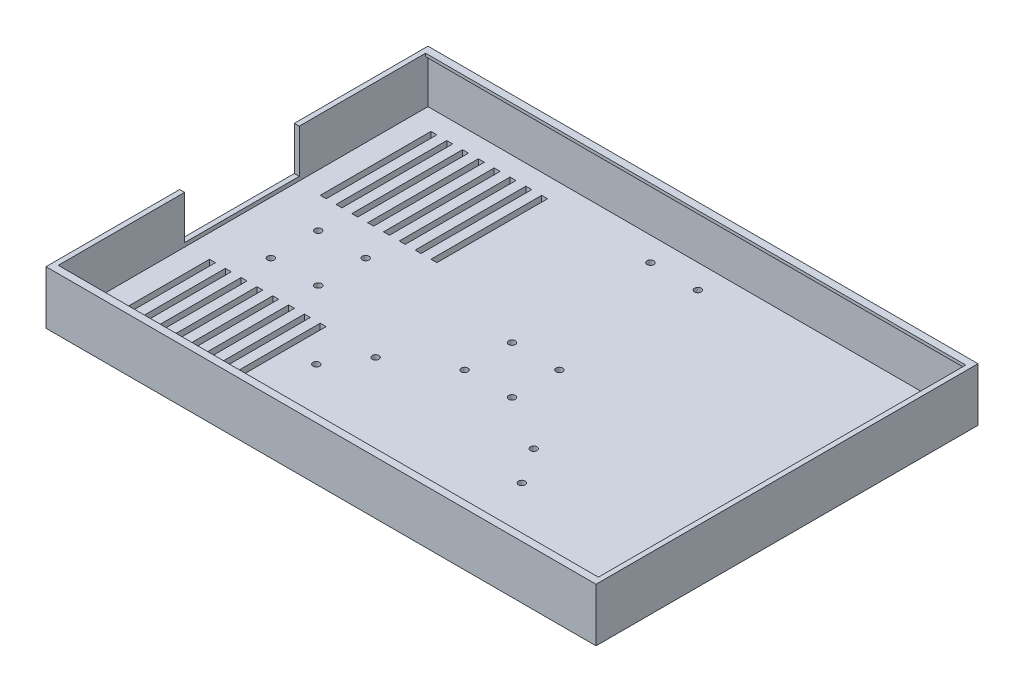
SolidWorks part; units mm, degrees
ref_plane "Front Plane" through (0, 0, 0) normal (0, 0, 1) x (1, 0, 0)
ref_plane "Top Plane" through (0, 0, 0) normal (0, 1, 0) x (1, 0, 0)
ref_plane "Right Plane" through (0, 0, 0) normal (1, 0, 0) x (0, 0, -1)
sketch "Sketch1" plane through (0, 0, 0) normal (0, 1, 0) x (1, 0, 0)
  line L1 (-139.1, -96.6) -> (139.1, -96.6)
  line L2 (-139.1, -96.6) -> (-139.1, 96.6)
  line L3 (-139.1, 96.6) -> (139.1, 96.6)
  line L4 (139.1, -96.6) -> (139.1, 96.6)
  line L5 (-139.1, -96.6) -> (139.1, 96.6) construction
  line L6 (-139.1, 96.6) -> (139.1, -96.6) construction
  point P0 (0, 0)
  dimension "D1" = 278.2
  dimension "D2" = 193.2
extrude "Shell Block" add sketch "Sketch1" along normal blind 27
ref_plane "Shell Front" through (0, 27, 0) normal (0, 1, 0) x (1, 0, 0)
sketch "Sketch2" plane through (0, 27, 0) normal (0, 1, 0) x (1, 0, 0)
  line L1 (-136.6, -92.9) -> (136.6, -92.9)
  line L2 (-136.6, -92.9) -> (-136.6, 92.9)
  line L3 (-136.6, 92.9) -> (136.6, 92.9)
  line L4 (136.6, -92.9) -> (136.6, 92.9)
  line L5 (-136.6, -92.9) -> (136.6, 92.9) construction
  line L6 (-136.6, 92.9) -> (136.6, -92.9) construction
  point P0 (0, 0)
  dimension "D1" = 273.2
  dimension "D2" = 185.8
extrude "Front Opening" cut sketch "Sketch2" against normal blind 1.5
ref_plane "Under Lip" through (0, 25.5, 0) normal (0, 1, 0) x (1, 0, 0)
sketch "Sketch3" plane through (0, 25.5, 0) normal (0, 1, 0) x (1, 0, 0)
  line L1 (-136.6, -94.1) -> (136.6, -94.1)
  line L2 (-136.6, -94.1) -> (-136.6, 94.1)
  line L3 (-136.6, 94.1) -> (136.6, 94.1)
  line L4 (136.6, -94.1) -> (136.6, 94.1)
  line L5 (-136.6, -94.1) -> (136.6, 94.1) construction
  line L6 (-136.6, 94.1) -> (136.6, -94.1) construction
  point P0 (0, 0)
  dimension "D1" = 273.2
  dimension "D2" = 188.2
extrude "Display Pocket" cut sketch "Sketch3" against normal blind 22.5
ref_plane "Back Inner" through (0, 3, 0) normal (0, 1, 0) x (1, 0, 0)
sketch "Sketch4" plane through (0, 3, 0) normal (0, 1, 0) x (1, 0, 0)
  line L1 (-69, 28) -> (-66, 28)
  line L2 (-69, 28) -> (-69, 84)
  line L3 (-69, 84) -> (-66, 84)
  line L4 (-66, 28) -> (-66, 84)
  line L6 (-69, -84) -> (-66, -84)
  line L7 (-69, -84) -> (-69, -28)
  line L8 (-69, -28) -> (-66, -28)
  line L9 (-66, -84) -> (-66, -28)
  line L11 (-77, 28) -> (-74, 28)
  line L12 (-77, 28) -> (-77, 84)
  line L13 (-77, 84) -> (-74, 84)
  line L14 (-74, 28) -> (-74, 84)
  line L16 (-77, -84) -> (-74, -84)
  line L17 (-77, -84) -> (-77, -28)
  line L18 (-77, -28) -> (-74, -28)
  line L19 (-74, -84) -> (-74, -28)
  line L21 (-85, 28) -> (-82, 28)
  line L22 (-85, 28) -> (-85, 84)
  line L23 (-85, 84) -> (-82, 84)
  line L24 (-82, 28) -> (-82, 84)
  line L26 (-85, -84) -> (-82, -84)
  line L27 (-85, -84) -> (-85, -28)
  line L28 (-85, -28) -> (-82, -28)
  line L29 (-82, -84) -> (-82, -28)
  line L31 (-93, 28) -> (-90, 28)
  line L32 (-93, 28) -> (-93, 84)
  line L33 (-93, 84) -> (-90, 84)
  line L34 (-90, 28) -> (-90, 84)
  line L36 (-93, -84) -> (-90, -84)
  line L37 (-93, -84) -> (-93, -28)
  line L38 (-93, -28) -> (-90, -28)
  line L39 (-90, -84) -> (-90, -28)
  line L41 (-101, 28) -> (-98, 28)
  line L42 (-101, 28) -> (-101, 84)
  line L43 (-101, 84) -> (-98, 84)
  line L44 (-98, 28) -> (-98, 84)
  line L46 (-101, -84) -> (-98, -84)
  line L47 (-101, -84) -> (-101, -28)
  line L48 (-101, -28) -> (-98, -28)
  line L49 (-98, -84) -> (-98, -28)
  line L51 (-109, 28) -> (-106, 28)
  line L52 (-109, 28) -> (-109, 84)
  line L53 (-109, 84) -> (-106, 84)
  line L54 (-106, 28) -> (-106, 84)
  line L56 (-109, -84) -> (-106, -84)
  line L57 (-109, -84) -> (-109, -28)
  line L58 (-109, -28) -> (-106, -28)
  line L59 (-106, -84) -> (-106, -28)
  line L61 (-117, 28) -> (-114, 28)
  line L62 (-117, 28) -> (-117, 84)
  line L63 (-117, 84) -> (-114, 84)
  line L64 (-114, 28) -> (-114, 84)
  line L66 (-117, -84) -> (-114, -84)
  line L67 (-117, -84) -> (-117, -28)
  line L68 (-117, -28) -> (-114, -28)
  line L69 (-114, -84) -> (-114, -28)
  line L71 (-125, 28) -> (-122, 28)
  line L72 (-125, 28) -> (-125, 84)
  line L73 (-125, 84) -> (-122, 84)
  line L74 (-122, 28) -> (-122, 84)
  line L76 (-125, -84) -> (-122, -84)
  line L77 (-125, -84) -> (-125, -28)
  line L78 (-125, -28) -> (-122, -28)
  line L79 (-122, -84) -> (-122, -28)
extrude "Vent Slots" cut sketch "Sketch4" against normal blind 4
sketch "Sketch5" plane through (0, 0, 0) normal (1, 0, 0) x (0, 0, -1)
  line L1 (-29, 5) -> (29, 5)
  line L2 (-29, 5) -> (-29, 28)
  line L3 (-29, 28) -> (29, 28)
  line L4 (29, 5) -> (29, 28)
extrude "Cable Exit (-X short side)" cut sketch "Sketch5" against normal blind 140.1
sketch "Sketch6" plane through (0, 3, 0) normal (0, 1, 0) x (1, 0, 0)
  circle A0 centre (-40, -29) radius 1.7
  circle A1 centre (-40, -89) radius 1.7
  circle A2 centre (40, -29) radius 1.7
  circle A3 centre (40, -89) radius 1.7
  circle A4 centre (-52, -47) radius 1.7
  circle A5 centre (-52, -71) radius 1.7
  circle A6 centre (52, -47) radius 1.7
  circle A7 centre (52, -71) radius 1.7
  circle A8 centre (-12, 82) radius 1.7
  circle A9 centre (12, 82) radius 1.7
  circle A10 centre (124, 12) radius 1.7
  circle A11 centre (124, -12) radius 1.7
  circle A12 centre (-12, 12) radius 1.7
  circle A13 centre (-12, -12) radius 1.7
  circle A14 centre (12, 12) radius 1.7
  circle A15 centre (12, -12) radius 1.7
  circle A16 centre (-110, -12) radius 1.7
  circle A17 centre (-110, 12) radius 1.7
  circle A18 centre (-86, -12) radius 1.7
  circle A19 centre (-86, 12) radius 1.7
extrude "Bolt Holes" cut sketch "Sketch6" against normal blind 4
equation "\"DispL\" = 272.0"
equation "\"DispW\" = 187.0"
equation "\"DispT\" = 20.0"
equation "\"Clr\" = 0.6"
equation "\"Wall\" = 2.5"
equation "\"BackT\" = 3.0"
equation "\"CableRoom\" = 4.0"
equation "\"LipW\" = 1.2"
equation "\"LipT\" = 1.5"
equation "\"CableW\" = 58.0"
equation "\"CableH\" = 16.0"
equation "\"BoltD\" = 3.4"
equation "\"ShellL\" = \"DispL\" + 2 * \"Clr\" + 2 * \"Wall\""
equation "\"ShellW\" = \"DispW\" + 2 * \"Clr\" + 2 * \"Wall\""
equation "\"ShellH\" = \"BackT\" + \"DispT\" + \"CableRoom\""
equation "\"D1@Sketch1\" = \"ShellL\""
equation "\"D2@Sketch1\" = \"ShellW\""
equation "\"D1@Shell Block\" = \"ShellH\""
equation "\"D1@Shell Front\" = \"ShellH\""
equation "\"D1@Sketch2\" = \"DispL\" + 2 * \"Clr\""
equation "\"D2@Sketch2\" = \"DispW\" + 2 * \"Clr\" - 2 * \"LipW\""
equation "\"D1@Front Opening\" = \"LipT\""
equation "\"D1@Under Lip\" = \"ShellH\" - \"LipT\""
equation "\"D1@Sketch3\" = \"DispL\" + 2 * \"Clr\""
equation "\"D2@Sketch3\" = \"DispW\" + 2 * \"Clr\""
equation "\"D1@Display Pocket\" = \"ShellH\" - \"LipT\" - \"BackT\""
equation "\"D1@Back Inner\" = \"BackT\""
